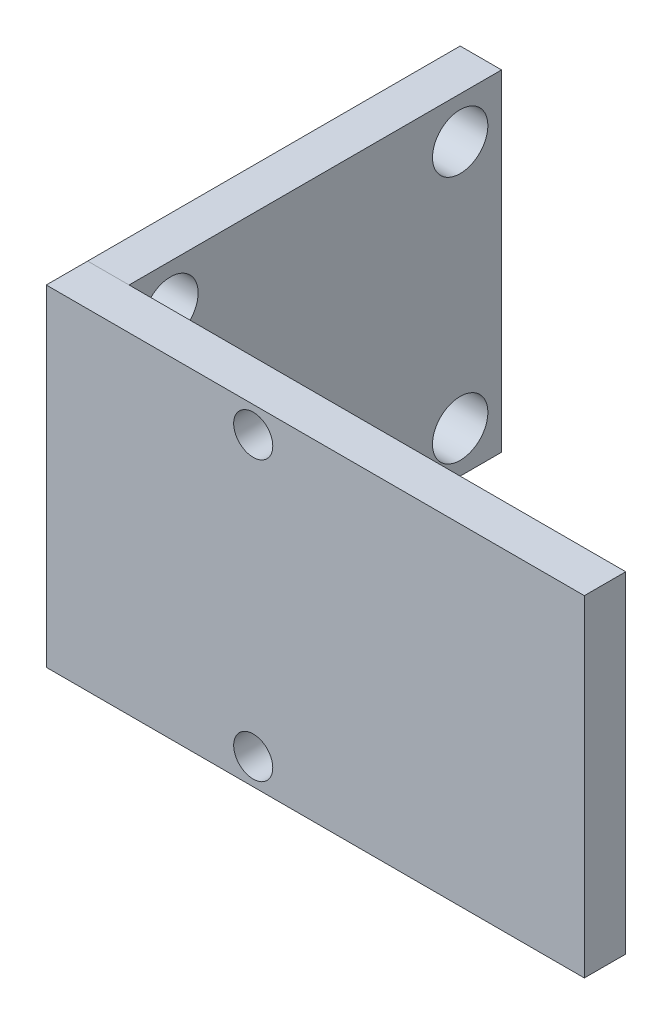
SolidWorks part; units mm, degrees
ref_plane "Front Plane" through (0, 0, 0) normal (0, 0, 1) x (1, 0, 0)
ref_plane "Top Plane" through (0, 0, 0) normal (0, 1, 0) x (1, 0, 0)
ref_plane "Right Plane" through (0, 0, 0) normal (1, 0, 0) x (0, 0, -1)
sketch "Sketch1" plane through (0, 0, 0) normal (1, 0, 0) x (0, 0, -1)
  line L0 (-31.8768, 23.0863) -> (-31.8768, -16.3439) construction
  line L2 (-44.5768, 4.0363) -> (-5.3691, 4.0363) construction
  line L4 (-43.3068, 14.1963) -> (-20.4468, 14.1963)
  line L5 (-40.7668, -3.5837) -> (-22.9868, -3.5837) construction
  line L6 (-40.7668, -3.5837) -> (-40.7668, 11.6563) construction
  line L7 (-40.7668, 11.6563) -> (-22.9868, 11.6563) construction
  line L8 (-22.9868, -3.5837) -> (-22.9868, 11.6563) construction
  line L9 (-40.7668, -3.5837) -> (-22.9868, 11.6563) construction
  line L10 (-40.7668, 11.6563) -> (-22.9868, -3.5837) construction
  line L11 (-20.4468, -6.1237) -> (-20.4468, 14.1963)
  line L12 (-43.3068, -6.1237) -> (-20.4468, -6.1237)
  line L13 (-43.3068, -6.1237) -> (-43.3068, 14.1963)
  point P1 (0, 0)
  point P16 (0, 0)
  point P17 (-31.8768, 4.0363)
  point P18 (0, 0)
  point P25 (0, 0)
  point P30 (0, 0)
  dimension "D1" = 2.54
extrude "side connecting to grip" add sketch "Sketch1" along normal blind 2.54 separate body
hole_wizard "M3 Clearance Hole1" positions "Sketch4" profile "Sketch5" hole size "M3" standard "ANSI Metric" end condition through all
sketch "Sketch4" plane through (2.54, 0, 0) normal (1, 0, 0) x (0, 0, -1)
  point P0 (-40.7668, 11.6563)
  point P3 (-22.9868, 11.6563)
  point P6 (-22.9868, -3.5837)
  point P9 (-40.7668, -3.5837)
sketch "Sketch5" plane through (2.54, 11.6563, 40.7668) normal (0, 1, 0) x (0, 0, -1)
  line L0 (0, 0) -> (0, 2.54)
  line L1 (0, 2.54) -> (1.7, 2.54)
  line L2 (1.7, 2.54) -> (1.7, 0)
  line L5 (1.7, 0) -> (0, 0)
  line L11 (0, -6.35) -> (0, 107.95) construction
  dimension "Thru Hole Dia." = 3.4
  dimension "Thru Hole Depth" = 2.54
sketch "Sketch6" plane through (2.54, 0, 0) normal (1, 0, 0) x (0, 0, -1)
  line L42 (-43.3068, 14.1963) -> (-45.8468, 14.1963)
  line L43 (-45.8468, 14.1963) -> (-45.8468, -6.1237)
  line L44 (-45.8468, -6.1237) -> (-43.3068, -6.1237)
  line L45 (-43.3068, -6.1237) -> (-43.3068, 14.1963) construction
  line L46 (-43.3068, 14.1963) -> (-43.3068, -6.1237)
  dimension "D1" = 2.54
extrude "side connecting to servo" add sketch "Sketch6" along normal blind 30.48 and the other way blind 2.54 separate body
sketch "servo holes" plane through (0, 0, 45.8468) normal (0, 0, 1) x (1, 0, 0)
  line L0 (0, 4.0363) -> (36.6866, 4.0363) construction
  line L1 (0, -6.1237) -> (0, 14.1963) construction
  circle A0 centre (12.7, 4.0363) radius 8.55 construction
  point P5 (12.7, -4.5137)
  point P8 (12.7, 12.5863)
  dimension "D1" = 17.1
  dimension "D2" = 12.7
hole_wizard "cutout servo holes" positions "Sketch8" profile "Sketch9" hole size "M2" standard "ANSI Metric" end condition through all
sketch "Sketch8" plane through (0, 0, 45.8468) normal (0, 0, 1) x (1, 0, 0)
  point P0 (12.7, 12.5863)
  point P3 (12.7, -4.5137)
sketch "Sketch9" plane through (12.7, 12.5863, 45.8468) normal (1, 0, 0) x (0, -1, 0)
  line L0 (0, 0) -> (0, 25.4)
  line L1 (0, 25.4) -> (1.2, 25.4)
  line L2 (1.2, 25.4) -> (1.2, 0)
  line L5 (1.2, 0) -> (0, 0)
  line L11 (0, -6.35) -> (0, 107.95) construction
  dimension "Thru Hole Dia." = 2.4
  dimension "Thru Hole Depth" = 25.4
